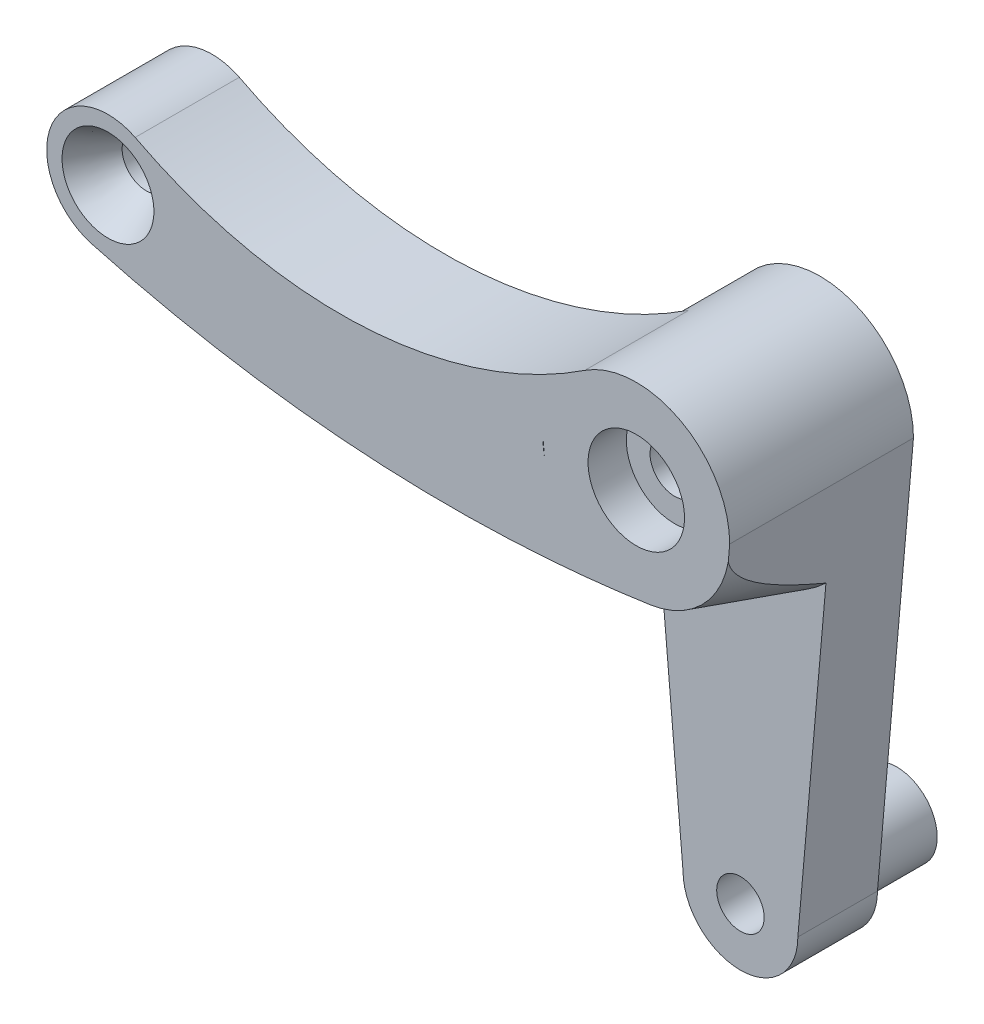
SolidWorks part; units mm, degrees
ref_plane "前视基准面" through (0, 0, 0) normal (0, 0, 1) x (1, 0, 0)
ref_plane "上视基准面" through (0, 0, 0) normal (0, 1, 0) x (1, 0, 0)
ref_plane "右视基准面" through (0, 0, 0) normal (1, 0, 0) x (0, 0, -1)
sketch "草图1" plane through (0, 0, 0) normal (0, 0, 1) x (1, 0, 0)
  line L0 (-3.75, -26.8) -> (-6.1, 0)
  line L1 (6.1, 0) -> (3.75, -26.8)
  arc A0 (6.1, 0) -> (-6.1, 0) centre (0, 0) ccw
  arc A1 (-3.75, -26.8) -> (3.75, -26.8) centre (0, -26.8) ccw
  circle A2 centre (0, 0) radius 1.6
  circle A3 centre (0, -26.8) radius 1.55
  dimension "D1" = 3.1
  dimension "D2" = 3.2
extrude "凸台-拉伸1" add sketch "草图1" along normal blind 12
sketch "草图3" plane through (0, 0, 12) normal (0, 0, 1) x (1, 0, 0)
  line L0 (-6.0069, -1.0616) -> (-3.75, -26.8)
  line L1 (3.75, -26.8) -> (6.0069, -1.0616)
  arc A0 (-6.0069, -1.0616) -> (6.0069, -1.0616) centre (0, 0) ccw
  arc A1 (-3.75, -26.8) -> (3.75, -26.8) centre (0, -26.8) ccw
extrude "切除-拉伸1" cut sketch "草图3" against normal blind 6.8
sketch "草图4" plane through (0, 0, 0) normal (0, 0, -1) x (-1, 0, 0)
  circle A0 centre (0, 0) radius 3.15
  dimension "D1" = 6.3
sketch "草图5" plane through (0, 0, 0) normal (0, 0, -1) x (-1, 0, 0)
  circle A0 centre (0, -26.8) radius 2.65
  circle A1 centre (0, -26.8) radius 1.55
  dimension "D1" = 5.3
  dimension "D2" = 3.1
extrude "凸台-拉伸2" add sketch "草图5" along normal blind 5
chamfer "倒角1" distance 0.5 distance2 0.5 1 edges at (2.65, -26.8, 0)
sketch "草图6" plane through (0, 0, 12) normal (0, 0, 1) x (1, 0, 0)
  circle A0 centre (0, 0) radius 1.6
  circle A1 centre (0, 0) radius 3.15
  dimension "D1" = 6.3
  dimension "D2" = 3.2
sketch "草图7" plane through (0, 0, 5.2) normal (0, 0, 1) x (1, 0, 0)
  line L0 (3.5514, 0) -> (-30.4486, 0) construction
  line L1 (-32.95, 0) -> (-34.5, 0) construction
  circle A0 centre (-34.5, 0) radius 1.575
  arc A1 (-3.365, 5.0879) -> (0.9013, -6.0331) centre (0, 0) ccw
  arc A2 (-32.7223, 3.5833) -> (-35.5572, -3.8578) centre (-34.5, 0) ccw
  arc A3 (-35.5572, -3.8578) -> (0.9013, -6.0331) centre (-12.1717, 81.4759) ccw
  arc A4 (-32.7223, 3.5833) -> (-3.365, 5.0879) centre (-19.3185, 29.2095) ccw
  dimension "D1" = 3.15
  dimension "D2" = 34.5
extrude "凸台-拉伸3" add sketch "草图7" along normal blind 6.8
chamfer "倒角2" distance 6.8 distance2 2 2 edges at (-2.2967, -6.4514, 5.2) (4.2555, -4.3704, 5.2) first distance on face at (-15.0102, -5.9571, 7.92) first distance on face at (3.8548, -3.9589, 8.6)
extrude "切除-拉伸2" cut sketch "草图4" against normal blind 2.5
extrude "切除-拉伸3" cut sketch "草图6" against normal blind 2.5
sketch "草图9" plane through (0, 0, 0) normal (0, 1, 0) x (1, 0, 0)
  line L4 (-36.075, -10.7686) -> (-34.5, -10.7686) construction
  line L5 (-34.5, -10.7686) -> (-34.5, -13.6615) construction
  line L6 (-35.5572, -12) -> (-5.5079, -12) construction
  line L7 (-31.5, -12) -> (-32.925, -9.5)
  line L8 (-32.925, -9.5) -> (-34.5, -9.5)
  line L9 (-34.5, -9.5) -> (-34.5, -12)
  line L10 (-34.5, -12) -> (-31.5, -12)
  point P7 (-34.5, -9.5)
  point P10 (-31.5, -12)
  dimension "D1" = 2.5
  dimension "D2" = 3
revolve "切除-旋转1" cut sketch "草图9" angle 360 about L9
